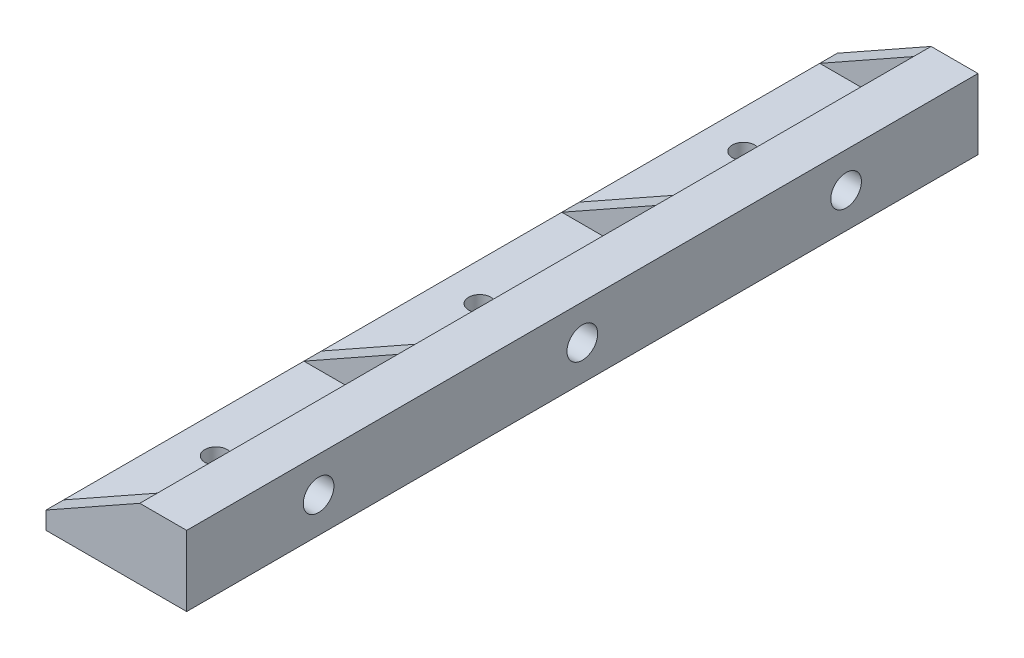
SolidWorks part; units mm, degrees
ref_plane "Front Plane" through (0, 0, 0) normal (0, 0, 1) x (1, 0, 0)
ref_plane "Top Plane" through (0, 0, 0) normal (0, 1, 0) x (1, 0, 0)
ref_plane "Right Plane" through (0, 0, 0) normal (1, 0, 0) x (0, 0, -1)
sketch "Sketch1" plane through (0, 0, 0) normal (0, 0, 1) x (1, 0, 0)
  line L0 (0, 0) -> (0, 12)
  line L1 (0, 12) -> (-8, 12)
  line L2 (-8, 12) -> (-8, 6)
  line L3 (-11, 3) -> (-24, 3)
  line L4 (-24, 3) -> (-24, 0)
  line L6 (-24, 0) -> (0, 0)
  arc A0 (-8, 6) -> (-11, 3) centre (-11, 6) cw
  dimension "D1" = 3
  dimension "D2" = 12
  dimension "D3" = 24
  dimension "D4" = 8
  dimension "D5" = 3
extrude "Boss-Extrude1" add sketch "Sketch1" along normal blind 135
ref_plane "Plane2" through (0, 0, 0) normal (0, 0, -1) x (-1, 0, 0)
ref_plane "Plane4" through (0, 0, 67.5) normal (0, 0, -1) x (-1, 0, 0)
ref_plane "Plane5" through (0, 0, 45.5) normal (0, 0, -1) x (-1, 0, 0)
sketch "Sketch4" plane through (0, 0, 45.5) normal (0, 0, -1) x (-1, 0, 0)
  line L0 (8, 12) -> (24, 3)
sketch "Sketch5" plane through (0, 0, 0) normal (0, 0, -1) x (-1, 0, 0)
  line L0 (8, 12) -> (24, 3)
rib "Rib3" sketch "Sketch4" sketch "Sketch4" thickness 3 extrusion direction parallel to sketch draft on no parameters "D1"=3
rib "Rib4" sketch "Sketch5" sketch "Sketch5" thickness 3 extrusion direction parallel to sketch draft on no parameters "D1"=3
mirror "Mirror1" about plane through (0, 0, 67.5) normal (0, 0, -1) of "Rib3", "Rib4"
sketch "Sketch6" plane through (0, 0, 0) normal (1, 0, 0) x (0, 0, -1)
  line L0 (-135, 6) -> (0, 6) construction
  line L1 (-135, 0) -> (-135, 12) construction
  line L2 (0, 0) -> (0, 12) construction
  circle A0 centre (-112.5, 6) radius 2.3495
  circle A1 centre (-67.5, 6) radius 2.3495
  circle A2 centre (-22.5, 6) radius 2.3495
  point P6 (-112.5, 6)
  point P7 (-22.5, 6)
  point P8 (-67.5, 6)
  dimension "D3" = 4.699
  dimension "D1" = 22.5
  dimension "D2" = 22.5
sketch "Sketch9" plane through (0, 0, 0) normal (0, -1, 0) x (1, 0, 0)
  line L0 (-17.5, 135) -> (-17.5, 0) construction
  line L1 (-24, 135) -> (0, 135) construction
  line L2 (-24, 0) -> (0, 0) construction
  line L3 (-24, 135) -> (-24, 0) construction
  point P6 (-17.5, 112.5)
  point P7 (-17.5, 22.5)
  point P10 (-17.5, 67.5)
  dimension "D1" = 22.5
  dimension "D2" = 22.5
  dimension "D3" = 6.5
hole_wizard "#6 Clearance Hole1" positions "Sketch10" profile "Sketch11" hole size "#6" standard "ANSI Inch" end condition through all
sketch "Sketch10" plane through (0, 0, 0) normal (0, -1, 0) x (-1, 0, 0)
  point P0 (17.5, -22.5)
  point P3 (17.5, -112.5)
  point P6 (17.5, -67.5)
sketch "Sketch11" plane through (-17.5, 0, 22.5) normal (1, 0, 0) x (0, 0, -1)
  line L0 (0, 0) -> (0, 12)
  line L1 (0, 12) -> (1.8986, 12)
  line L2 (1.8986, 12) -> (1.8986, 0)
  line L5 (1.8986, 0) -> (0, 0)
  line L11 (0, -6.35) -> (0, 107.95) construction
  dimension "Thru Hole Dia." = 3.7973
  dimension "Thru Hole Depth" = 12
extrude "Cut-Extrude1" cut sketch "Sketch6" against normal offset from surface (7 mm away) 1 up to face at (-8, 9, 111.5)
sketch "Sketch12" plane through (0, 0, 0) normal (1, 0, 0) x (0, 0, -1)
  circle A0 centre (-112.5, 6) radius 2.6162
  circle A1 centre (-67.5, 6) radius 2.6162
  circle A2 centre (-22.5, 6) radius 2.6162
  dimension "D1" = 5.2324
extrude "Cut-Extrude2" cut sketch "Sketch12" against normal blind 6.35
equation "\"length\"= \"D1@Boss-Extrude1\""
equation "\"D2@Sketch6\"= \"length\" / 6"
equation "\"D1@Sketch6\"= \"length\" / 6"
equation "\"D1@Plane5\"= ( \"length\" - \"D1@Rib4\" ) / 6"
equation "\"D2@Sketch9\"= \"length\" / 6"
equation "\"D1@Sketch9\"= \"length\" / 6"
